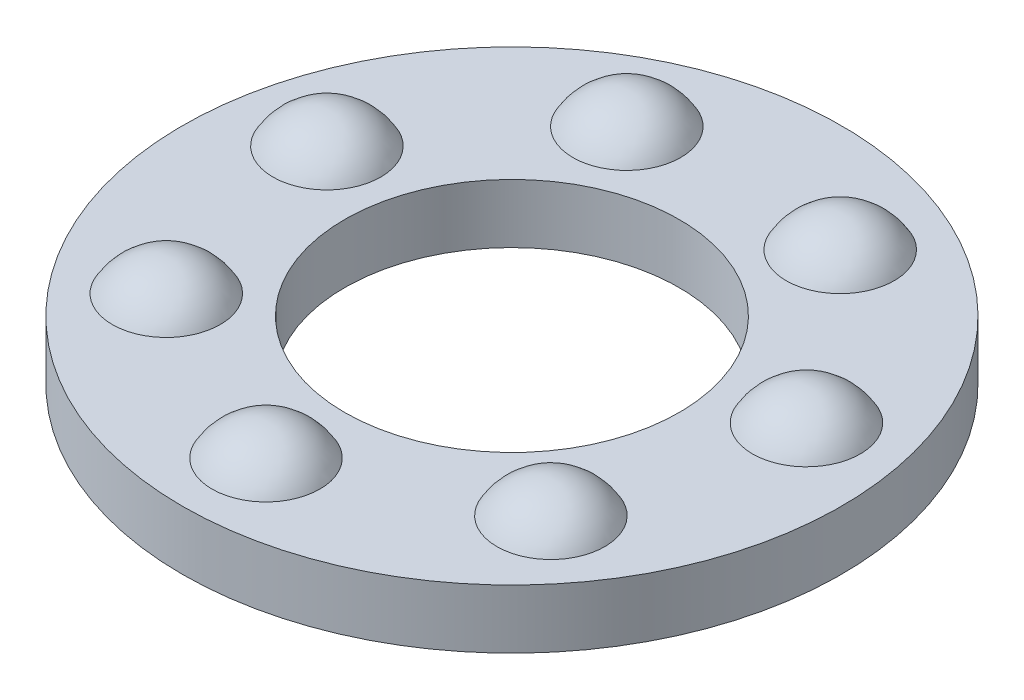
SolidWorks part; units mm, degrees
ref_plane "Front Plane" through (0, 0, 0) normal (0, 0, 1) x (1, 0, 0)
ref_plane "Top Plane" through (0, 0, 0) normal (0, 1, 0) x (1, 0, 0)
ref_plane "Right Plane" through (0, 0, 0) normal (1, 0, 0) x (0, 0, -1)
sketch "Sketch1" plane through (0, 0, 0) normal (1, 0, 0) x (0, 0, -1)
  line L0 (-2.5, 0.625) -> (-2.5, -0.625)
  arc A0 (-2.5, 0.625) -> (-2.5, -0.625) centre (-2.5, 0) ccw
  dimension "D2" = 1.25
  dimension "D1" = 2.5
revolve "Revolve1" add sketch "Sketch1" angle 360 about L0
ref_axis "Axis1" through (0, 0.6875, 0) along (0, -1, 0)
sketch "Sketch2" plane through (0, 0, 0) normal (0, 1, 0) x (1, 0, 0)
  circle A0 centre (0, 0) radius 1.7
  circle A1 centre (0, 0) radius 3.35
  dimension "D1" = 3.4
  dimension "D2" = 6.7
extrude "Boss-Extrude1" add sketch "Sketch2" along normal mid plane 0.6
pattern_circular "CirPattern2" count 7 over 360 about axis through (0, 0.6875, 0) along (0, -1, 0) of "Revolve1"
